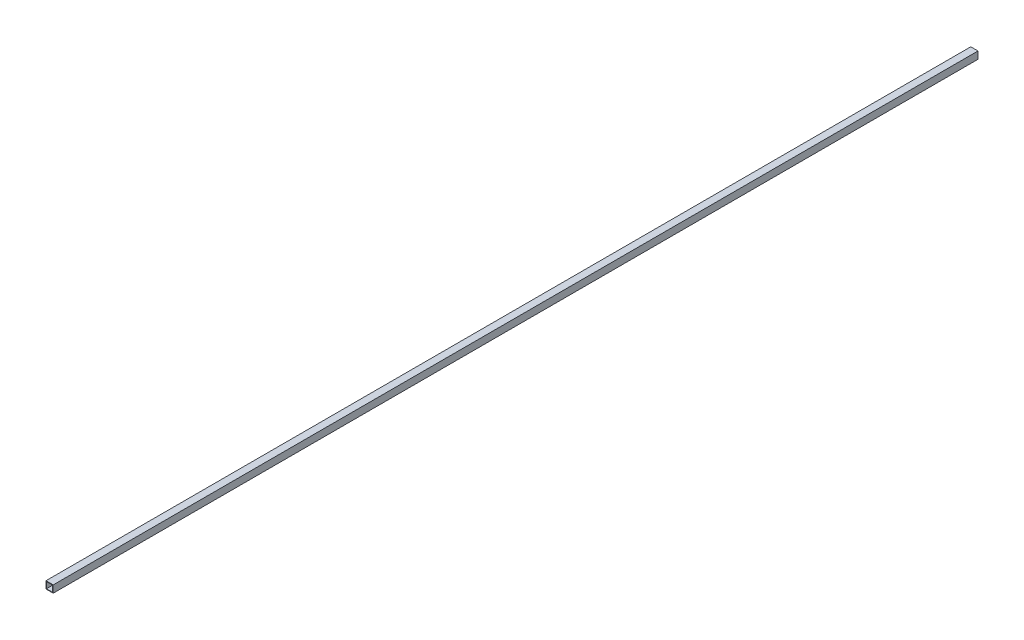
SolidWorks part; units mm, degrees
ref_plane "Front Plane" through (0, 0, 0) normal (0, 0, 1) x (1, 0, 0)
ref_plane "Top Plane" through (0, 0, 0) normal (0, 1, 0) x (1, 0, 0)
ref_plane "Right Plane" through (0, 0, 0) normal (1, 0, 0) x (0, 0, -1)
sketch "Sketch1" plane through (0, 0, 0) normal (0, 0, 1) x (1, 0, 0)
  line L0 (-11.8872, 17.272) -> (-14.478, 17.272) construction
  line L1 (-11.8872, 11.8872) -> (-11.8872, 17.272) construction
  line L2 (-17.272, 11.8872) -> (-11.8872, 11.8872) construction
  line L3 (-17.272, 14.478) -> (-17.272, 11.8872) construction
  line L4 (14.478, 17.272) -> (11.8872, 17.272) construction
  line L5 (17.272, 11.8872) -> (17.272, 14.478) construction
  line L6 (11.8872, 11.8872) -> (17.272, 11.8872) construction
  line L7 (11.8872, 17.272) -> (11.8872, 11.8872) construction
  line L8 (11.8872, -17.272) -> (14.478, -17.272) construction
  line L9 (11.8872, -11.8872) -> (11.8872, -17.272) construction
  line L10 (17.272, -11.8872) -> (11.8872, -11.8872) construction
  line L11 (17.272, -14.478) -> (17.272, -11.8872) construction
  line L12 (-14.478, -17.272) -> (-11.8872, -17.272) construction
  line L13 (-17.272, -11.8872) -> (-17.272, -14.478) construction
  line L14 (-11.8872, -11.8872) -> (-17.272, -11.8872) construction
  line L15 (-11.8872, -17.272) -> (-11.8872, -11.8872) construction
  line L16 (-6.731, 4.5757) -> (-6.731, -4.5757) construction
  line L17 (-6.731, -4.5757) -> (-12.4423, -10.287) construction
  line L18 (-12.4423, -10.287) -> (-15.6718, -10.287) construction
  line L19 (-15.6718, -10.287) -> (-15.6718, -6.858) construction
  line L20 (-15.6718, -6.858) -> (-14.478, -6.858) construction
  line L21 (-14.478, -6.858) -> (-14.478, -4.064) construction
  line L22 (-14.478, -4.064) -> (-19.05, -4.064) construction
  line L23 (-19.05, -4.064) -> (-19.05, -15.875) construction
  line L24 (-15.875, -19.05) -> (-4.064, -19.05) construction
  line L25 (-4.064, -19.05) -> (-4.064, -14.478) construction
  line L26 (-4.064, -14.478) -> (-6.858, -14.478) construction
  line L27 (-6.858, -14.478) -> (-6.858, -15.6718) construction
  line L28 (-6.858, -15.6718) -> (-10.287, -15.6718) construction
  line L29 (-10.287, -15.6718) -> (-10.287, -12.4423) construction
  line L30 (-10.287, -12.4423) -> (-4.5757, -6.731) construction
  line L31 (-4.5757, -6.731) -> (4.5757, -6.731) construction
  line L32 (4.5757, -6.731) -> (10.287, -12.4423) construction
  line L33 (10.287, -12.4423) -> (10.287, -15.6718) construction
  line L34 (10.287, -15.6718) -> (6.858, -15.6718) construction
  line L35 (6.858, -15.6718) -> (6.858, -14.478) construction
  line L36 (6.858, -14.478) -> (4.064, -14.478) construction
  line L37 (4.064, -14.478) -> (4.064, -19.05) construction
  line L38 (4.064, -19.05) -> (15.875, -19.05) construction
  line L39 (19.05, -15.875) -> (19.05, -4.064) construction
  line L40 (19.05, -4.064) -> (14.478, -4.064) construction
  line L41 (14.478, -4.064) -> (14.478, -6.858) construction
  line L42 (14.478, -6.858) -> (15.6718, -6.858) construction
  line L43 (15.6718, -6.858) -> (15.6718, -10.287) construction
  line L44 (15.6718, -10.287) -> (12.4423, -10.287) construction
  line L45 (12.4423, -10.287) -> (6.731, -4.5757) construction
  line L46 (6.731, -4.5757) -> (6.731, 4.5757) construction
  line L47 (6.731, 4.5757) -> (12.4423, 10.287) construction
  line L48 (12.4423, 10.287) -> (15.6718, 10.287) construction
  line L49 (15.6718, 10.287) -> (15.6718, 6.858) construction
  line L50 (15.6718, 6.858) -> (14.478, 6.858) construction
  line L51 (14.478, 6.858) -> (14.478, 4.064) construction
  line L52 (14.478, 4.064) -> (19.05, 4.064) construction
  line L53 (19.05, 4.064) -> (19.05, 15.875) construction
  line L54 (15.875, 19.05) -> (4.064, 19.05) construction
  line L55 (4.064, 19.05) -> (4.064, 14.478) construction
  line L56 (4.064, 14.478) -> (6.858, 14.478) construction
  line L57 (6.858, 14.478) -> (6.858, 15.6718) construction
  line L58 (6.858, 15.6718) -> (10.287, 15.6718) construction
  line L59 (10.287, 15.6718) -> (10.287, 12.4423) construction
  line L60 (10.287, 12.4423) -> (4.5757, 6.731) construction
  line L61 (4.5757, 6.731) -> (-4.5757, 6.731) construction
  line L62 (-4.5757, 6.731) -> (-10.287, 12.4423) construction
  line L63 (-10.287, 12.4423) -> (-10.287, 15.6718) construction
  line L64 (-10.287, 15.6718) -> (-6.858, 15.6718) construction
  line L65 (-6.858, 15.6718) -> (-6.858, 14.478) construction
  line L66 (-6.858, 14.478) -> (-4.064, 14.478) construction
  line L67 (-4.064, 14.478) -> (-4.064, 19.05) construction
  line L68 (-4.064, 19.05) -> (-15.875, 19.05) construction
  line L69 (-19.05, 15.875) -> (-19.05, 4.064) construction
  line L70 (-19.05, 4.064) -> (-14.478, 4.064) construction
  line L71 (-14.478, 4.064) -> (-14.478, 6.858) construction
  line L72 (-14.478, 6.858) -> (-15.6718, 6.858) construction
  line L73 (-15.6718, 6.858) -> (-15.6718, 10.287) construction
  line L74 (-15.6718, 10.287) -> (-12.4423, 10.287) construction
  line L75 (-12.4423, 10.287) -> (-6.731, 4.5757) construction
  line L77 (-9.525, 9.525) -> (9.525, 9.525)
  line L78 (-9.525, 9.525) -> (-9.525, -9.525)
  line L79 (-9.525, -9.525) -> (9.525, -9.525)
  line L80 (9.525, 9.525) -> (9.525, -9.525)
  line L81 (-9.525, 9.525) -> (9.525, -9.525) construction
  line L82 (-9.525, -9.525) -> (9.525, 9.525) construction
  line L83 (-8.255, 8.255) -> (8.255, 8.255)
  line L84 (-8.255, 8.255) -> (-8.255, -8.255)
  line L85 (-8.255, -8.255) -> (8.255, -8.255)
  line L86 (8.255, 8.255) -> (8.255, -8.255)
  line L87 (-8.255, 8.255) -> (8.255, -8.255) construction
  line L88 (-8.255, -8.255) -> (8.255, 8.255) construction
  circle A0 centre (0, 0) radius 3.2639 construction
  arc A1 (-19.05, -15.875) -> (-15.875, -19.05) centre (-15.875, -15.875) ccw construction
  arc A2 (15.875, -19.05) -> (19.05, -15.875) centre (15.875, -15.875) ccw construction
  arc A3 (19.05, 15.875) -> (15.875, 19.05) centre (15.875, 15.875) ccw construction
  arc A4 (-15.875, 19.05) -> (-19.05, 15.875) centre (-15.875, 15.875) ccw construction
  arc A5 (-14.478, 17.272) -> (-17.272, 14.478) centre (-14.478, 14.478) ccw construction
  arc A6 (17.272, 14.478) -> (14.478, 17.272) centre (14.478, 14.478) ccw construction
  arc A7 (14.478, -17.272) -> (17.272, -14.478) centre (14.478, -14.478) ccw construction
  arc A8 (-17.272, -14.478) -> (-14.478, -17.272) centre (-14.478, -14.478) ccw construction
  dimension "D1" = 19.05
  dimension "D2" = 19.05
  dimension "D3" = 1.27
extrude "Boss-Extrude1" add sketch "Sketch1" along normal mid plane 2438.4
sketch "Sketch2" plane through (9.525, 0, 0) normal (1, 0, 0) x (0, 0, -1)
  line L0 (-1219.2, 9.525) -> (1219.2, 9.525) construction
  line L1 (-1219.2, -9.525) -> (762, -9.525)
  line L2 (-1219.2, -9.525) -> (-1219.2, 9.525)
  line L3 (-1219.2, 9.525) -> (762, 9.525)
  line L4 (762, -9.525) -> (762, 9.525)
  dimension "D1" = 457.2
extrude "Cut-Extrude1" [suppressed] cut sketch "Sketch2" against normal through all
